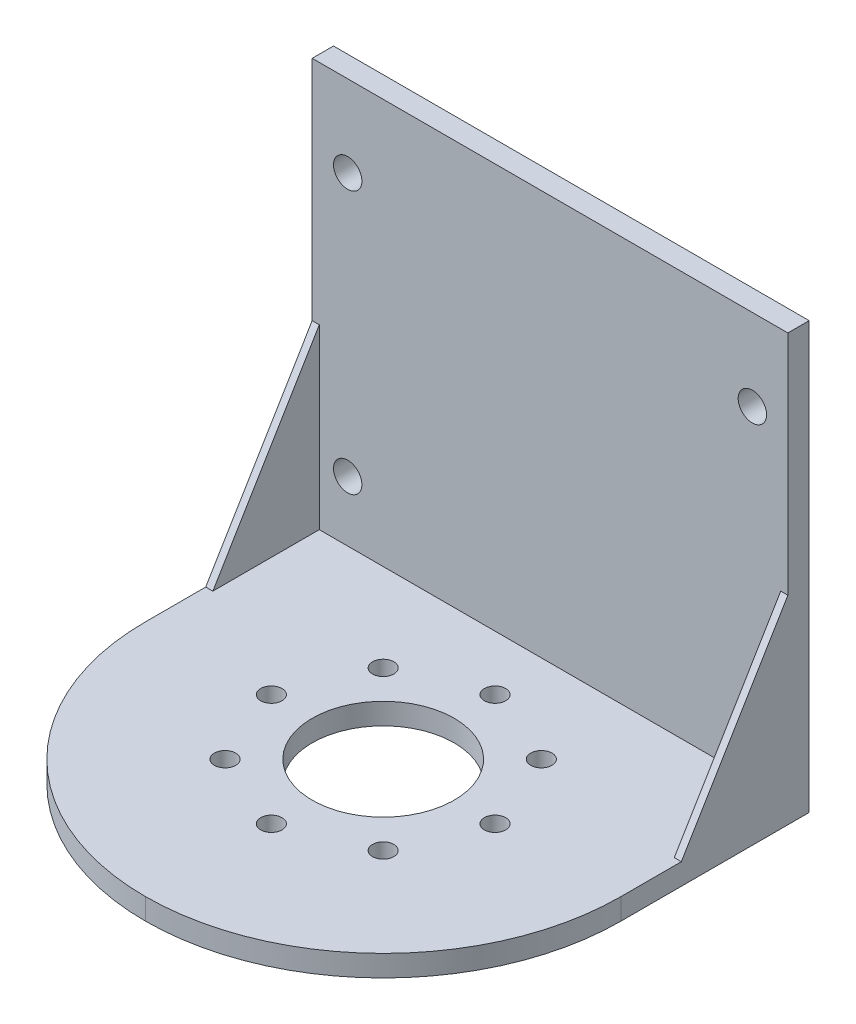
SolidWorks part; units mm, degrees
material "AISI 1010 Steel, hot rolled bar"
ref_plane "Front Plane" through (0, 0, 0) normal (0, 0, 1) x (1, 0, 0)
ref_plane "Top Plane" through (0, 0, 0) normal (0, 1, 0) x (1, 0, 0)
ref_plane "Right Plane" through (0, 0, 0) normal (1, 0, 0) x (0, 0, -1)
sketch "Sketch1" plane through (0, 0, 0) normal (0, 0, 1) x (1, 0, 0)
  line L0 (0, 30) -> (0, -30) construction
  line L1 (-33.5, -30) -> (33.5, -30)
  line L2 (-33.5, -30) -> (-33.5, 30)
  line L3 (-33.5, 30) -> (33.5, 30)
  line L4 (33.5, -30) -> (33.5, 30)
  line L5 (-33.5, -30) -> (33.5, 30) construction
  line L6 (-33.5, 30) -> (33.5, -30) construction
  line L7 (-33.5, 0) -> (33.5, 0) construction
  circle A0 centre (-28.5, 18.5166) radius 2
  circle A1 centre (28.5, 18.5166) radius 2
  circle A2 centre (28.5, -18.5166) radius 2
  circle A3 centre (-28.5, -18.5166) radius 2
  point P0 (0, 0)
  dimension "D3" = 4
  dimension "D1" = 67
  dimension "D2" = 60
  dimension "D4" = 5
extrude "Boss-Extrude1" add sketch "Sketch1" along normal blind 3
sketch "Sketch2" plane through (0, 0, 3) normal (0, 0, 1) x (1, 0, 0)
  line L0 (33.5, -30) -> (33.5, 30) construction
  line L1 (-33.5, -30) -> (33.5, -30)
  line L2 (-33.5, -30) -> (-33.5, -27)
  line L3 (-33.5, -27) -> (33.5, -27)
  line L4 (33.5, -30) -> (33.5, -27)
  line L5 (-33.5, -30) -> (33.5, -27) construction
  line L6 (-33.5, -27) -> (33.5, -30) construction
  line L7 (-33.5, -30) -> (33.5, -30) construction
  point P0 (0, -28.5)
  dimension "D1" = 1.5
  dimension "D2" = 67
  dimension "D3" = 3
extrude "Boss-Extrude2" add sketch "Sketch2" along normal blind 57
fillet "Fillet1" radius 33.5 2 edges at (-33.5, -28.5, 60) (33.5, -28.5, 60)
sketch "Sketch3" plane through (0, -30, 0) normal (0, -1, 0) x (1, 0, 0)
  circle A0 centre (0, 26.5) radius 10
  circle A1 centre (0, 42.2524) radius 1.5
  circle A2 centre (11.1386, 37.6386) radius 1.5
  circle A3 centre (15.7524, 26.5) radius 1.5
  circle A4 centre (11.1386, 15.3614) radius 1.5
  circle A5 centre (0, 10.7476) radius 1.5
  circle A6 centre (-11.1386, 15.3614) radius 1.5
  circle A7 centre (-15.7524, 26.5) radius 1.5
  circle A8 centre (-11.1386, 37.6386) radius 1.5
  point P21 (0, 26.5)
  dimension "D1" = 20
  dimension "D2" = 3
  dimension "D3" = 8
extrude "Cut-Extrude1" cut sketch "Sketch3" against normal blind 57
sketch "Sketch4" plane through (-33.5, 0, 0) normal (-1, 0, 0) x (0, 0, 1)
  line L0 (3, -2) -> (18, -27)
  line L1 (3, 30) -> (3, -27) construction
  line L2 (3, -2) -> (3, -27)
  line L3 (26.5, -27) -> (3, -27) construction
  line L4 (3, -27) -> (18, -27)
  dimension "D1" = 25
  dimension "D2" = 15
extrude "Boss-Extrude3" add sketch "Sketch4" against normal blind 1
extrude "Boss-Extrude4" add sketch "Sketch4<2>" against normal blind 1 from offset 66 offset against normal yes
sketch "Sketch4<2>" plane through (-33.5, 0, 0) normal (-1, 0, 0) x (0, 0, 1) same geometry as "Sketch4"
